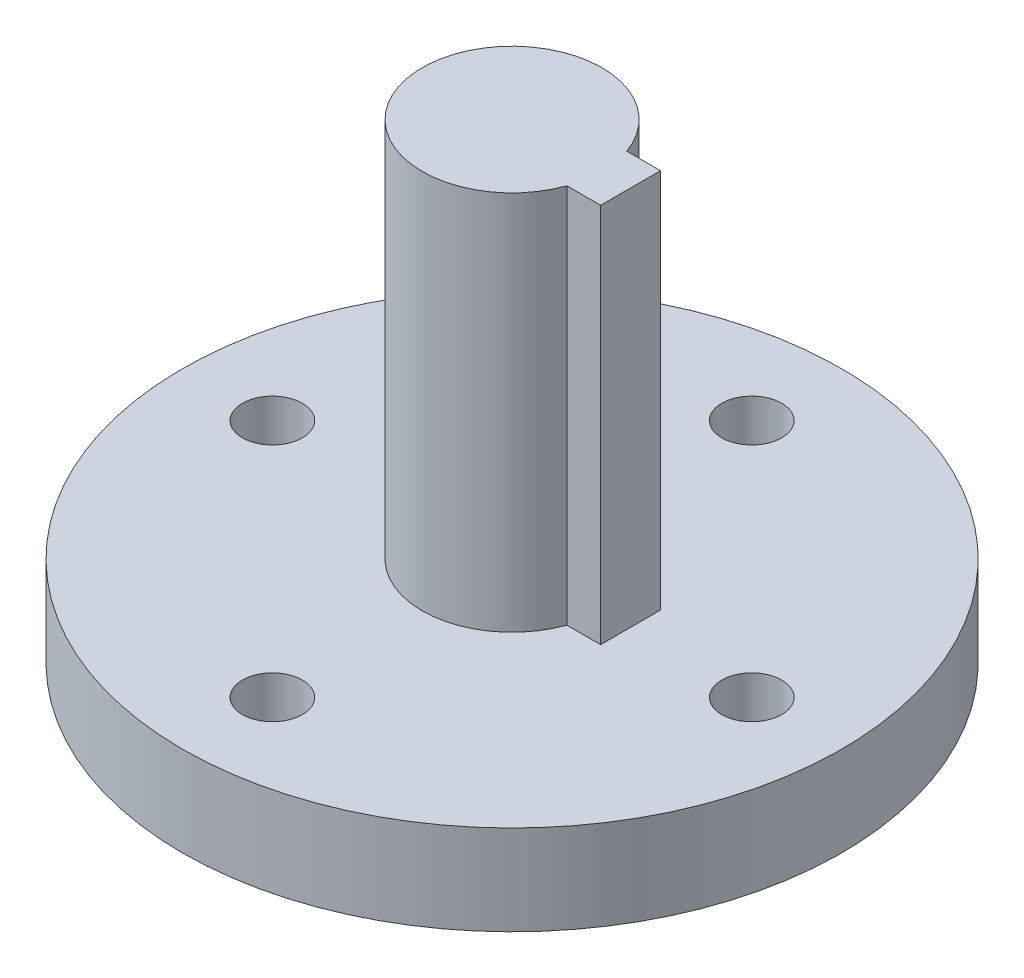
SolidWorks part; units mm, degrees
ref_plane "Front Plane" through (0, 0, 0) normal (0, 0, 1) x (1, 0, 0)
ref_plane "Top Plane" through (0, 0, 0) normal (0, 1, 0) x (1, 0, 0)
ref_plane "Right Plane" through (0, 0, 0) normal (1, 0, 0) x (0, 0, -1)
sketch "Sketch1" plane through (0, 0, 0) normal (0, 1, 0) x (1, 0, 0)
  line L0 (0, 0) -> (0, 8) construction
  circle A0 centre (0, 0) radius 11
  circle A1 centre (0, 8) radius 1
  circle A2 centre (8, 0) radius 1
  circle A3 centre (0, -8) radius 1
  circle A4 centre (-8, 0) radius 1
  point P6 (0, 0)
  point P7 (0, 0)
  dimension "D1" = 22
  dimension "D2" = 2
  dimension "D5" = 8
  dimension "D4" = 4
extrude "Boss-Extrude1" add sketch "Sketch1" along normal blind 3
sketch "Sketch2" plane through (0, 3, 0) normal (0, 1, 0) x (1, 0, 0)
  line L0 (2.8284, 1) -> (3.9554, 1)
  line L1 (3.9554, 1) -> (3.9554, -1)
  line L2 (3.9554, -1) -> (2.8284, -1)
  arc A0 (2.8284, 1) -> (2.8284, -1) centre (0, 0) ccw
  dimension "D1" = 6
  dimension "D2" = 2
  dimension "D3" = 1.127
extrude "Boss-Extrude2" add sketch "Sketch2" along normal blind 12.7
